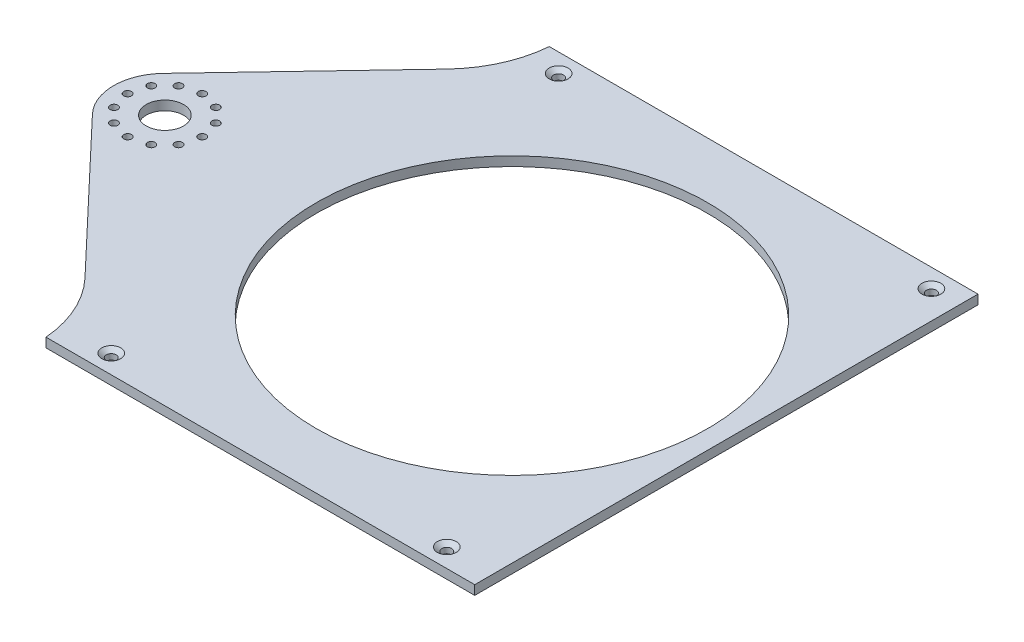
SolidWorks part; units mm, degrees
material "6061-T6 (SS)"
ref_plane "Front Plane" through (0, 0, 0) normal (0, 0, 1) x (1, 0, 0)
ref_plane "Top Plane" through (0, 0, 0) normal (0, 1, 0) x (1, 0, 0)
ref_plane "Right Plane" through (0, 0, 0) normal (1, 0, 0) x (0, 0, -1)
sketch "Sketch1" plane through (0, 0, 0) normal (0, 1, 0) x (1, 0, 0)
  line L0 (0, 0) -> (0, 133.35) construction
  line L1 (0, 133.35) -> (0, 171.45) construction
  line L2 (0, 171.45) -> (146.05, 171.45)
  line L3 (133.35, 0) -> (146.05, 0) construction
  line L4 (146.05, 0) -> (146.05, 171.45)
  line L5 (0, 146.05) -> (74.5442, 146.05) construction
  line L6 (0, 171.45) -> (-146.05, 171.45)
  line L7 (-146.05, 171.45) -> (-146.05, 0) construction
  line L8 (133.35, 0) -> (-146.05, 0) construction
  line L9 (-146.05, 0) -> (-146.05, -171.45) construction
  line L10 (-146.05, -171.45) -> (146.05, -171.45)
  line L11 (146.05, -171.45) -> (146.05, 0)
  line L12 (0, -133.35) -> (0, -171.45) construction
  line L13 (0, 0) -> (-236.4969, 0) construction
  line L14 (-236.4969, 0) -> (-236.4969, 25.4) construction
  line L17 (-261.8308, -24.0406) -> (-146.05, -146.05)
  line L18 (-146.05, -171.45) -> (-146.05, -146.05)
  line L19 (-261.8308, 24.0406) -> (-146.05, 146.05)
  line L20 (-146.05, 146.05) -> (-146.05, 171.45)
  circle A0 centre (0, 0) radius 133.35
  circle A2 centre (-236.4969, 0) radius 12.7
  circle A3 centre (-236.4969, 25.4) radius 2.6289
  circle A4 centre (-223.7969, 21.997) radius 2.6289
  circle A5 centre (-214.4998, 12.7) radius 2.6289
  circle A6 centre (-211.0969, 0) radius 2.6289
  circle A7 centre (-214.4998, -12.7) radius 2.6289
  circle A8 centre (-223.7969, -21.997) radius 2.6289
  circle A9 centre (-236.4969, -25.4) radius 2.6289
  circle A10 centre (-249.1969, -21.997) radius 2.6289
  circle A11 centre (-258.4939, -12.7) radius 2.6289
  circle A12 centre (-261.8969, 0) radius 2.6289
  circle A13 centre (-258.4939, 12.7) radius 2.6289
  circle A14 centre (-249.1969, 21.997) radius 2.6289
  arc A15 (-261.8308, -24.0406) -> (-261.8308, 24.0406) centre (-236.4969, 0) cw
  point P8 (-133.35, 0)
  point P45 (-236.4969, 0)
  dimension "D1" = 266.7
  dimension "D2" = 12.7
  dimension "D8" = 25.4
  dimension "D9" = 5.2578
  dimension "D12" = 34.925
  dimension "D3" = 38.1
  dimension "D4" = 25.4
  dimension "D5" = 12.7
  dimension "D6" = 38.1
  dimension "D7" = 236.4969
  dimension "D10" = 25.4
  dimension "D13" = 25.4
  dimension "D14" = 25.4
  dimension "D11" = 12
extrude "Extrude & center hole" add sketch "Sketch1" along normal blind 6.35
hole_wizard "CSK for 1/4 Flat Head Machine Screw (100)1" positions "Sketch4" profile "Sketch5" countersink size "1/4" standard "ANSI Inch" end condition through all
sketch "Sketch4" plane through (0, 6.35, 0) normal (0, 1, 0) x (1, 0, 0)
  line L0 (-146.05, -171.45) -> (146.05, -171.45) construction
  line L2 (146.05, -171.45) -> (146.05, 171.45) construction
  line L3 (146.05, 171.45) -> (-146.05, 171.45) construction
  line L4 (-146.05, 171.45) -> (-146.05, 146.05) construction
  line L5 (-146.05, -146.05) -> (-146.05, -171.45) construction
  point P0 (-114.3, -158.75)
  point P2 (114.3, -158.75)
  point P4 (127, 158.75)
  point P6 (-127, 158.75)
  dimension "D1" = 12.7
  dimension "D2" = 31.75
  dimension "D3" = 31.75
  dimension "D4" = 12.7
  dimension "D5" = 12.7
  dimension "D6" = 19.05
  dimension "D7" = 12.7
  dimension "D8" = 19.05
sketch "Sketch5" plane through (-114.3, 6.35, 158.75) normal (1, 0, 0) x (0, 0, 1)
  line L0 (0, 0) -> (0, 6.35)
  line L1 (0, 6.35) -> (3.3782, 6.35)
  line L2 (3.3782, 6.35) -> (3.3782, 2.5682)
  line L3 (3.3782, 2.5682) -> (6.4389, 0)
  line L5 (6.4389, 0) -> (0, 0)
  line L6 (-3.3782, 2.5682) -> (-6.4389, 0) construction
  line L11 (0, -6.35) -> (0, 107.95) construction
  dimension "Thru Hole Dia." = 6.7564
  dimension "Thru Hole Depth" = 6.35
  dimension "Near C'Sink Dia." = 12.8778
  dimension "Near C'Sink Angle" = 100
fillet "Fillet1" radius 79.7965 2 edges at (-146.05, 3.175, 146.05) (-146.05, 3.175, -146.05)
sketch "Sketch6" plane through (0, 6.35, 0) normal (0, 1, 0) x (1, 0, 0)
  line L0 (-138.6896, -16.7717) -> (-237.6096, 40.3398)
  line L1 (-237.6096, 40.3398) -> (-137.296, 146.05)
  line L2 (-167.679, 123.2575) -> (-261.8308, 24.0406) construction
  line L3 (-137.296, 146.05) -> (-12.7777, 146.05)
  line L4 (0, 0) -> (-12.1757, 139.1684) construction
  line L5 (-12.1757, 139.1684) -> (-12.7777, 146.05)
  line L6 (0, 0) -> (0, 34.3566) construction
  line L7 (-236.4969, 0) -> (-219.3074, 29.773) construction
  line L8 (-222.4824, 24.2737) -> (-194.6467, 8.2028) construction
  line L9 (0, 0) -> (-97.1768, 0) construction
  line L10 (-237.6096, -40.3398) -> (-137.296, -146.05)
  line L11 (-138.6896, 16.7717) -> (-237.6096, -40.3398)
  line L12 (-12.1757, -139.1684) -> (-12.7777, -146.05)
  line L13 (-137.296, -146.05) -> (-12.7777, -146.05)
  line L14 (0, 0) -> (12.1757, 139.1684) construction
  line L15 (139.7, 24.6329) -> (139.7, 146.05)
  line L16 (146.05, -171.45) -> (146.05, 171.45) construction
  line L17 (0, 0) -> (137.5776, 24.2587) construction
  line L18 (137.5776, 24.2587) -> (139.7, 24.6329)
  line L19 (-12.7777, 146.05) -> (139.7, 146.05) construction
  line L20 (139.7, 146.05) -> (12.7777, 146.05)
  line L21 (12.1757, 139.1684) -> (12.7777, 146.05)
  line L22 (137.5776, -24.2587) -> (139.7, -24.6329)
  line L23 (139.7, -24.6329) -> (139.7, -146.05)
  line L24 (139.7, -146.05) -> (12.7777, -146.05)
  line L25 (12.1757, -139.1684) -> (12.7777, -146.05)
  arc A0 (-138.6896, -16.7717) -> (-12.1757, 139.1684) centre (0, 0) cw
  circle A1 centre (0, 0) radius 133.35 construction
  circle A2 centre (-127, 158.75) radius 6.4389 construction
  arc A3 (12.1757, -139.1684) -> (137.5776, -24.2587) centre (0, 0) ccw
  circle A5 centre (-223.7969, 21.997) radius 2.6289 construction
  arc A6 (-138.6896, 16.7717) -> (-12.1757, -139.1684) centre (0, 0) ccw
  arc A7 (12.1757, 139.1684) -> (137.5776, 24.2587) centre (0, 0) cw
  point P22 (-223.7969, 21.997)
  dimension "D1" = 6.35
  dimension "D7" = 6.35
  dimension "D2" = 6.35
  dimension "D3" = 12.7
  dimension "D4" = 5
  dimension "D5" = 6.35
  dimension "D6" = 5
  dimension "D8" = 6.35
  dimension "D9" = 170
extrude "Slotting" [suppressed] cut sketch "Sketch6" against normal through all
fillet "Fillet5" [suppressed] radius 3.9688
fillet "Fillet6" [suppressed] radius 3.9688
fillet "Fillet7" [suppressed] radius 3.9688
fillet "Fillet8" [suppressed] radius 3.9688
sketch "Sketch7" [suppressed] plane through (0, 6.35, 0) normal (0, 1, 0) x (1, 0, 0)
  line L0 (-138.6754, 16.8888) -> (-136.4208, 146.05)
  line L1 (-131.8114, 46.2802) -> (-130.0699, 146.05)
  line L2 (-16.4144, 146.05) -> (-136.4208, 146.05) construction
  line L3 (-136.4208, 146.05) -> (-130.0699, 146.05)
  line L4 (0, 0) -> (-133.35, 0) construction
  line L5 (-138.6754, -16.8888) -> (-136.4208, -146.05)
  line L6 (-136.4208, -146.05) -> (-130.0699, -146.05)
  line L7 (-131.8114, -46.2802) -> (-130.0699, -146.05)
  arc A0 (-16.0154, 138.7789) -> (-138.7628, 16.1548) centre (0, 0) ccw construction
  arc A1 (-131.8114, 46.2802) -> (-138.6754, 16.8888) centre (0, 0) ccw
  circle A2 centre (0, 0) radius 133.35 construction
  arc A3 (-131.8114, -46.2802) -> (-138.6754, -16.8888) centre (0, 0) cw
  dimension "D1" = 6.35
  dimension "D2" = 91
extrude "Motor side supports" [suppressed] add sketch "Sketch7" against normal up to surface (6.35 mm away) up to face at (-114.3, 0, 162.1282)
sketch "Sketch9" plane through (0, 6.35, 0) normal (0, 1, 0) x (1, 0, 0)
  line L0 (146.05, 0) -> (158.75, 0) construction
  line L1 (146.05, -171.45) -> (146.05, 171.45) construction
  line L2 (146.05, 171.45) -> (146.05, -171.45)
  arc A0 (146.05, 171.45) -> (146.05, -171.45) centre (-1004.8875, 0) cw
  dimension "D1" = 12.7
extrude "Opposite motor side thickening" [suppressed] add sketch "Sketch9" against normal up to surface (6.35 mm away) up to face at (-114.3, 0, 162.1282)
sketch "Sketch10" [suppressed] plane through (0, 6.35, 0) normal (0, 1, 0) x (1, 0, 0)
  line L0 (-194.6325, 42.0114) -> (-144.6893, 13.1767) construction
  line L1 (-136.4208, 146.05) -> (-138.6754, 16.8888) construction
  line L4 (-133.35, 0) -> (-209.4484, 0) construction
  line L7 (-138.1227, 48.5516) -> (-138.6754, 16.8888)
  line L8 (-153.6095, 18.3267) -> (-144.6893, 13.1767)
  line L9 (-153.6095, -18.3267) -> (-144.6893, -13.1767)
  line L10 (-138.1227, -48.5516) -> (-138.6754, -16.8888)
  circle A3 centre (0, 0) radius 133.35 construction
  circle A4 centre (-222.1484, 0) radius 12.7 construction
  arc A7 (-153.6095, 18.3267) -> (-138.1227, 48.5516) centre (-191.9464, 57.0501) ccw
  arc A8 (-144.6893, 13.1767) -> (-138.7628, 16.1548) centre (-142.7049, 16.6137) ccw construction
  arc A9 (-138.6754, 16.8888) -> (-138.7628, 16.1548) centre (0, 0) ccw construction
  arc A10 (-144.6893, 13.1767) -> (-138.7628, 16.1548) centre (-142.7049, 16.6137) ccw
  arc A11 (-138.6754, 16.8888) -> (-138.7628, 16.1548) centre (0, 0) ccw
  arc A12 (-138.6754, -16.8888) -> (-138.7628, -16.1548) centre (0, 0) cw
  arc A13 (-144.6893, -13.1767) -> (-138.7628, -16.1548) centre (-142.7049, -16.6137) cw
  arc A14 (-153.6095, -18.3267) -> (-138.1227, -48.5516) centre (-191.9464, -57.0501) cw
extrude "Motor side thickening" [suppressed] add sketch "Sketch10" against normal up to surface (6.35 mm away) up to face at (-114.3, 0, 162.1282)
